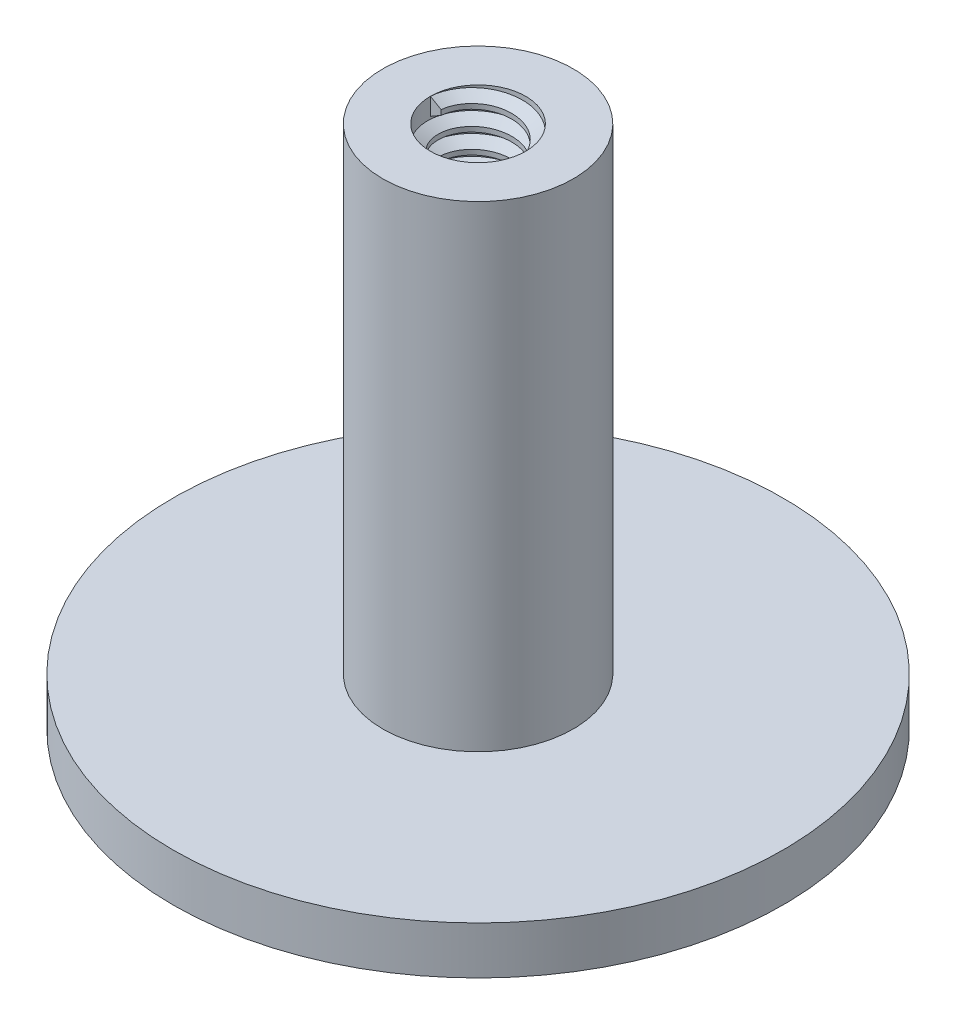
SolidWorks part; units mm, degrees
material "PE High Density"
ref_plane "Front Plane" through (0, 0, 0) normal (0, 0, 1) x (1, 0, 0)
ref_plane "Top Plane" through (0, 0, 0) normal (0, 1, 0) x (1, 0, 0)
ref_plane "Right Plane" through (0, 0, 0) normal (1, 0, 0) x (0, 0, -1)
sketch "Sketch1" plane through (0, 0, 0) normal (0, 1, 0) x (1, 0, 0)
  circle A0 centre (0, 0) radius 16.256
extrude "Boss-Extrude2" add sketch "Sketch1" along normal blind 2.54
sketch "Sketch3" plane through (0, 2.54, 0) normal (0, 1, 0) x (1, 0, 0)
  circle A0 centre (0, 0) radius 5.08
extrude "Boss-Extrude4" add sketch "Sketch3" along normal blind 25.4
sketch "Sketch4" plane through (0, 27.94, 0) normal (0, 1, 0) x (1, 0, 0)
  circle A0 centre (0, 0) radius 2.54
extrude "Cut-Extrude1" cut sketch "Sketch4" against normal blind 24.13
thread "Thread1" pitch 1.0583 method extrude profile "Thread Profile1" start angle 0, offset 0, length 20.32, pitch 1.0583, diameter 5.08
ref_plane "Plane1" through (-2.54, 27.94, 0) normal (0, 0, 1) x (-1, 0, 0)
sketch "Thread Profile1" plane through (-2.54, 27.94, 0) normal (0, 0, 1) x (-1, 0, 0)
  line L0 (0, 0) -> (0, 1.0583) construction
  line L11 (0, 0) -> (0, 0.926)
  line L12 (0, 0.926) -> (-0.5728, 0.5953)
  line L13 (-0.5728, 0.5953) -> (-0.5728, 0.3307)
  line L15 (-0.5728, 0.3307) -> (0, 0)
  line L17 (-0.5728, 0.463) -> (0, 0.463) construction
  point P2 (0, 0)
  dimension "Pitch" = 1.0583
  dimension "Profile_Angle" = 60
  dimension "Profile_Land" = 0.2646
  dimension "Profile_Height" = 0.5728
